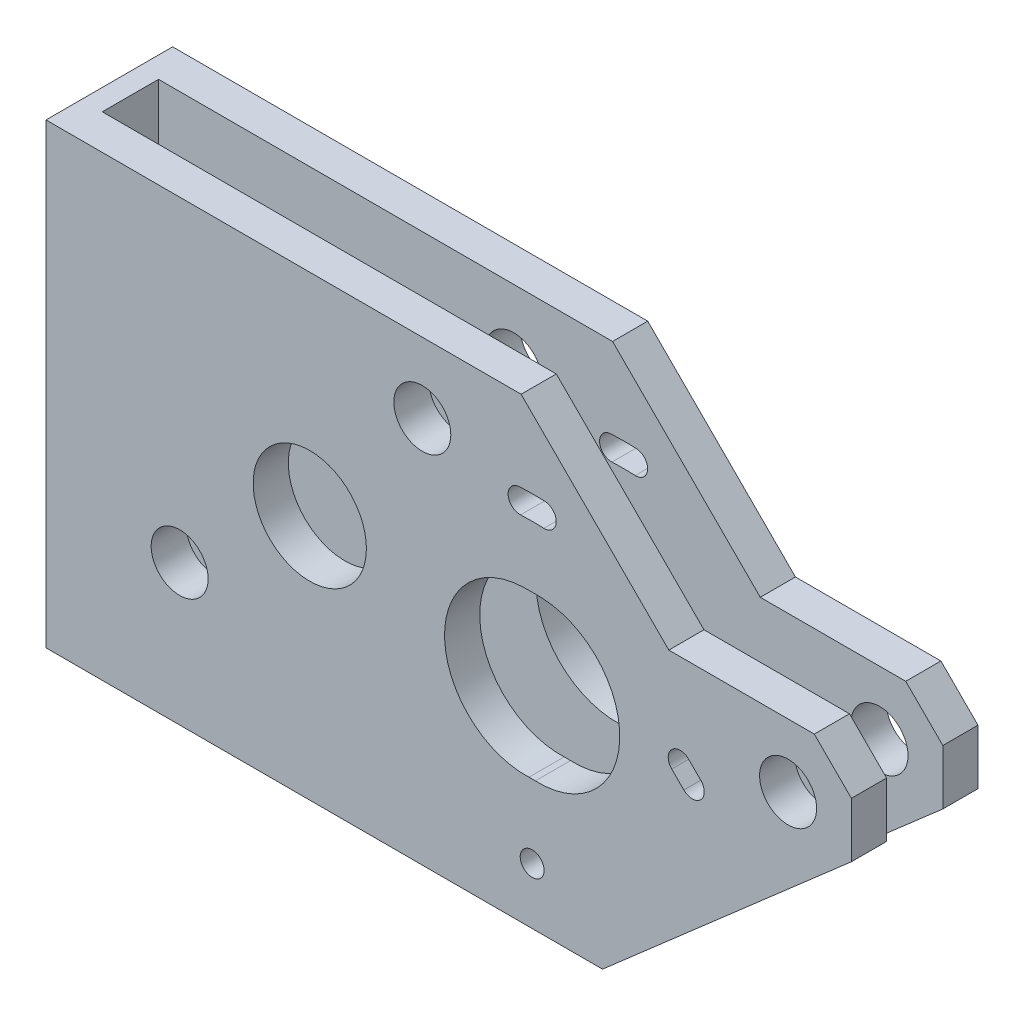
SolidWorks part; units mm, degrees
ref_plane "Front Plane" through (0, 0, 0) normal (0, 0, 1) x (1, 0, 0)
ref_plane "Top Plane" through (0, 0, 0) normal (0, 1, 0) x (1, 0, 0)
ref_plane "Right Plane" through (0, 0, 0) normal (1, 0, 0) x (0, 0, -1)
sketch "Sketch1" plane through (0, 0, 0) normal (0, 0, 1) x (1, 0, 0)
  line L0 (29.8964, 16.8072) -> (31.6176, -27) construction
  line L1 (31.6176, -27) -> (33.3388, 16.8072) construction
  line L2 (31.6176, -27) -> (31.6176, 16.841) construction
  line L3 (29.8964, 16.8072) -> (31.6176, -27) construction
  line L4 (31.6176, -27) -> (33.3388, 16.8072) construction
  line L5 (-37.5, 51.7917) -> (-37.5, -35) construction
  line L6 (-36.8694, -35) -> (81.0635, -35) construction
  line L7 (31.6176, -5.0795) -> (52.6603, -4.2343) construction
  line L8 (31.6176, -5.0795) -> (54.3818, -5.954) construction
  line L9 (53.8618, -3.0316) -> (55.5833, -4.7513)
  line L10 (53.1803, -7.1567) -> (51.4589, -5.437)
  line L11 (31.6176, -5.0795) -> (68, 0) construction
  line L12 (30.0455, 30) -> (-37.5, 30)
  line L13 (-37.5, 30) -> (-37.5, -35)
  line L14 (-37.5, -35) -> (41.6176, -35)
  line L15 (41.6176, -35) -> (77, -4.0881)
  line L18 (30.6614, -5.1004) -> (31.6176, -27) construction
  line L19 (31.6176, -27) -> (32.5737, -5.1004) construction
  line L20 (77, -4.0881) -> (77, 3.7279)
  line L21 (77, 3.7279) -> (71.7279, 9)
  line L22 (71.7279, 9) -> (51.0455, 9)
  line L23 (51.0455, 9) -> (30.0455, 30)
  circle A2 centre (0, 0) radius 10 construction
  circle A3 centre (0, 0) radius 2.5 construction
  circle A4 centre (0, 0) radius 17.8254 construction
  circle A5 centre (16, 20) radius 4.05
  circle A6 centre (68, 0) radius 4.05
  circle A7 centre (-18.5, -15) radius 4.05
  arc A9 (29.8964, 16.8072) -> (33.3388, 16.8072) centre (31.6176, -27) cw construction
  arc A10 (29.8296, 18.5059) -> (33.4055, 18.5059) centre (31.6176, -27) cw
  arc A11 (29.9631, 15.1085) -> (33.272, 15.1085) centre (31.6176, -27) cw
  arc A12 (29.8296, 18.5059) -> (29.9631, 15.1085) centre (29.8964, 16.8072) ccw
  arc A13 (33.4055, 18.5059) -> (33.272, 15.1085) centre (33.3388, 16.8072) cw
  circle A14 centre (31.6176, -27) radius 1.7
  arc A19 (51.4589, -5.437) -> (53.8618, -3.0316) centre (52.6603, -4.2343) cw
  arc A20 (53.1803, -7.1567) -> (55.5833, -4.7513) centre (54.3818, -5.954) ccw
  circle A21 centre (31.6176, -5.0795) radius 4.4563 construction
  circle A23 centre (0, 0) radius 8.05
  arc A25 (30.1598, 6.3887) -> (33.0754, 6.3887) centre (31.6176, -27) cw
  arc A26 (31.163, -16.5894) -> (32.0721, -16.5894) centre (31.6176, -27) cw
  arc A27 (30.1598, 6.3887) -> (31.163, -16.5894) centre (30.6614, -5.1004) ccw
  arc A28 (33.0754, 6.3887) -> (32.0721, -16.5894) centre (32.5737, -5.1004) cw
  arc A29 (30.6614, -5.1004) -> (32.5737, -5.1004) centre (31.6176, -27) cw construction
  circle A30 centre (68, 0) radius 11 construction
  point P14 (31.6176, 16.841)
  point P15 (31.6176, -5.0795)
  point P17 (0, 0)
  point P24 (31.6176, 15.141)
  point P50 (31.6176, -5.0795)
  dimension "D1" = 35.6507
  dimension "D2" = 20
  dimension "D3" = 5
  dimension "D4" = 8.1
  dimension "D12" = 1.7
  dimension "D20" = 8.9127
  dimension "D28" = 16.1
  dimension "D29" = 11.5
  dimension "D31" = 22
  dimension "D5" = 16
  dimension "D6" = 20
  dimension "D7" = 52
  dimension "D8" = 15
  dimension "D9" = 18.5
  dimension "D10" = 4.5
  dimension "D11" = 43.841
  dimension "D13" = 32.023
  dimension "D14" = 19
  dimension "D15" = 20
  dimension "D17" = 92.3
  dimension "D16" = 4.5
  dimension "D18" = 21.0597
  dimension "D19" = 22.781
  dimension "D21" = 8
  dimension "D24" = 10
  dimension "D27" = 10
  dimension "D30" = 5
  dimension "D22" = 135
  dimension "D23" = 135
  dimension "D25" = 7
  dimension "D26" = 9
  dimension "D32" = 9
  dimension "D33" = 9
  dimension "D34" = 9
extrude "Boss-Extrude1" add sketch "Sketch1" along normal blind 5
sketch "Sketch2" plane through (0, 0, 5) normal (0, 0, 1) x (1, 0, 0)
  line L0 (-37.5, 30) -> (-37.5, -35)
  line L1 (-37.5, -35) -> (41.6176, -35)
  line L2 (41.6176, -35) -> (41.6176, -32)
  line L3 (41.6176, -32) -> (-34.5, -32)
  line L4 (-34.5, -32) -> (-34.5, 30)
  line L5 (30.0455, 30) -> (-37.5, 30) construction
  line L6 (-34.5, 30) -> (-37.5, 30)
  dimension "D1" = 3
  dimension "D2" = 3
extrude "Boss-Extrude2" add sketch "Sketch2" along normal blind 8
extrude "Boss-Extrude3" add sketch "Sketch1<2>" along normal blind 5 from surface starting at face at (-10.1275, -12.3333, 13)
sketch "Sketch1<2>" plane through (0, 0, 0) normal (0, 0, 1) x (1, 0, 0) same geometry as "Sketch1"
equation "\"D1@Sketch1\"=(16*3.5*2)/pi"
